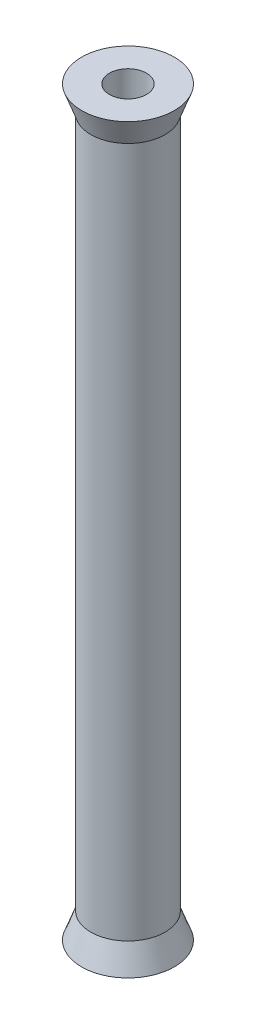
SolidWorks part; units mm, degrees
material "PET"
ref_plane "Front Plane" through (0, 0, 0) normal (0, 0, 1) x (1, 0, 0)
ref_plane "Top Plane" through (0, 0, 0) normal (0, 1, 0) x (1, 0, 0)
ref_plane "Right Plane" through (0, 0, 0) normal (1, 0, 0) x (0, 0, -1)
other "Configuration Table"
sketch "Sketch1" plane through (0, 0, 0) normal (0, 0, 1) x (1, 0, 0)
  line L0 (0, 0) -> (0, -50000) construction
  line L2 (2, -40) -> (5, -40)
  line L3 (2, 40) -> (5, 40)
  line L4 (4, -37.2525) -> (4, 37.2525)
  line L5 (2, 40) -> (2, -40)
  line L8 (5.5, 0) -> (-5.5, 0) construction
  line L9 (5, 40) -> (4, 37.2525)
  line L10 (5, -40) -> (4, -37.2525)
  point P4 (0, 0)
  dimension "Length" = 80
  dimension "D2" = 10
  dimension "D3" = 8
  dimension "ThreadDia" = 4
  dimension "D1" = 70
revolve "Revolve1" add sketch "Sketch1" angle 360 about L0
equation "\"D3@Sketch1\"= \"ThreadDia@Sketch1\" * 2"
equation "\"D2@Sketch1\"= \"ThreadDia@Sketch1\" * 2.5"
